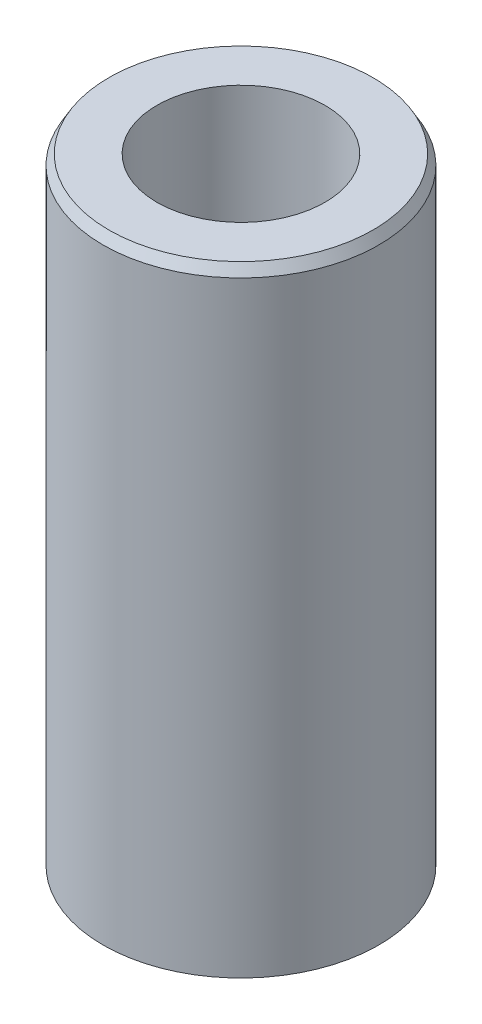
SolidWorks part; units mm, degrees
ref_plane "Front Plane" through (0, 0, 0) normal (0, 0, 1) x (1, 0, 0)
ref_plane "Top Plane" through (0, 0, 0) normal (0, 1, 0) x (1, 0, 0)
ref_plane "Right Plane" through (0, 0, 0) normal (1, 0, 0) x (0, 0, -1)
sketch "Sketch1" plane through (0, 0, 0) normal (0, 1, 0) x (1, 0, 0)
  circle A0 centre (0, 0) radius 57.5
  dimension "SHAFT_OD" = 115
extrude "Boss-Extrude1" add sketch "Sketch1" along normal blind 259.4944
sketch "Sketch2" plane through (0, 0, 0) normal (0, 1, 0) x (1, 0, 0)
  circle A0 centre (0, 0) radius 35.0618
  dimension "BORE_D" = 70.1236
extrude "Cut-Extrude1" cut sketch "Sketch2" along normal through all
chamfer "Chamfer1" distance 4.1963 angle 30 2 edges at (0, 259.4944, 57.5) (0, 0, 57.5) first distance on face at (0, 259.4944, 57.5) first distance on face at (0, 0, 35.0618)
